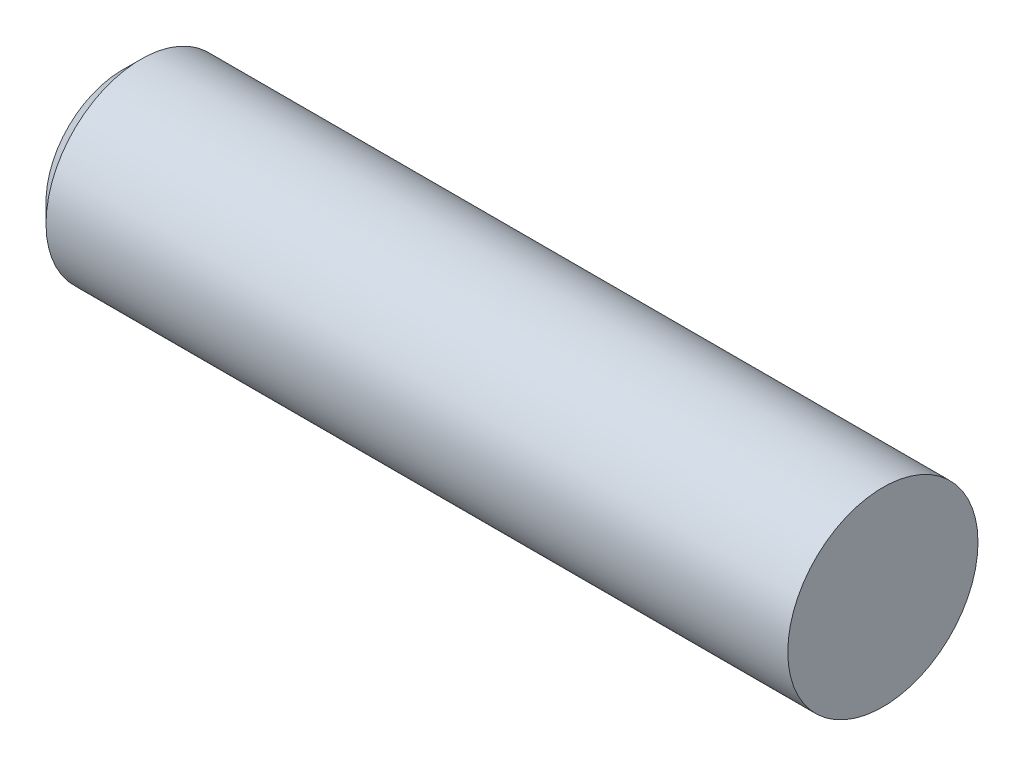
SolidWorks part; units mm, degrees
material "Cast Alloy Steel"
ref_plane "Front" through (0, 0, 0) normal (0, 0, 1) x (1, 0, 0)
ref_plane "Top" through (0, 0, 0) normal (0, 1, 0) x (1, 0, 0)
ref_plane "Right" through (0, 0, 0) normal (1, 0, 0) x (0, 0, -1)
sketch "Sketch1" plane through (0, 0, 0) normal (0, 0, 1) x (1, 0, 0)
  line L0 (-4.7625, 0) -> (4.7625, 0) construction
  line L1 (4.7625, 1.1906) -> (4.7625, -1.1906) construction
  line L2 (-4.7625, 1.1906) -> (-4.7625, -1.1906) construction
  dimension "Length" = 9.525
  dimension "Diameter" = 2.3813
sketch "Sketch2" plane through (0, 0, 0) normal (1, 0, 0) x (0, 0, -1)
  circle A0 centre (0, 0) radius 1.1906
extrude "Extrude1" add sketch "Sketch2" against normal up to vertex (4.7625 mm away) and the other way up to vertex (4.7625 mm away) up to point (-4.7625, 1.1906, 0) other way up to point (4.7625, 1.1906, 0)
chamfer "Chamfer1" distance 0.2381 angle 45 2 edges at (4.7625, 0, -1.1906) (-4.7625, 0, -1.1906)
other "DeleteFace1" face at (4.5244, 0, -1.1906) and patch yes
equation "\"D1@Chamfer1\" = \"Diameter@Sketch1\"*.1"
